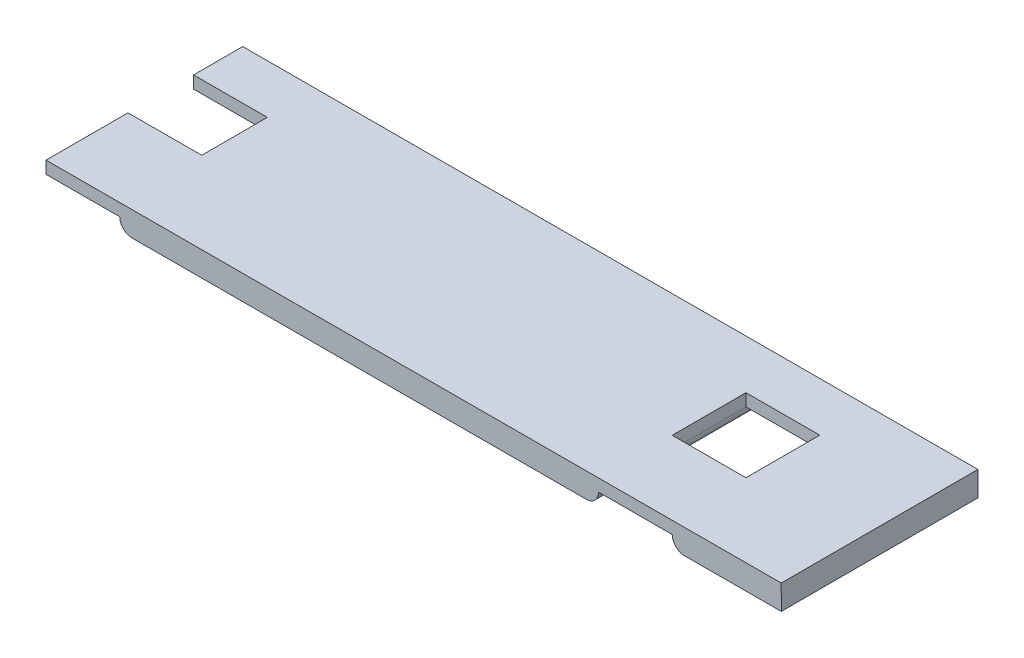
SolidWorks part; units mm, degrees
material "ABS"
ref_plane "X-Y Datum" through (0, 0, 0) normal (0, 0, 1) x (1, 0, 0)
ref_plane "X-Z Datum" through (0, 0, 0) normal (0, 1, 0) x (1, 0, 0)
ref_plane "Y-Z Datum" through (0, 0, 0) normal (1, 0, 0) x (0, 0, -1)
sketch "Sketch7" plane through (0, 0, -1997.112) normal (0, 0, 1) x (1, 0, 0)
  line L0 (-4.5317, 346.4377) -> (19.0716, 346.4821) construction
  line L1 (19.0603, 352.4821) -> (-7.543, 352.432) construction
  line L2 (-7.543, 352.432) -> (-7.5374, 349.432) construction
  line L3 (-4.5317, 346.4377) -> (19.0716, 346.4821)
  line L4 (-25.5373, 349.3981) -> (-25.543, 352.3981)
  line L5 (-25.543, 352.3981) -> (-142.3377, 352.178)
  line L6 (-142.3377, 352.178) -> (-142.332, 349.178)
  line L7 (-139.3264, 346.1836) -> (-28.5317, 346.3924)
  line L8 (-25.5373, 349.3981) -> (-25.543, 352.3981)
  line L9 (-25.543, 352.3981) -> (-142.3377, 352.178)
  line L10 (-142.3377, 352.178) -> (-142.332, 349.178)
  line L11 (-139.3264, 346.1836) -> (-28.5317, 346.3924)
  line L12 (19.0603, 352.4821) -> (-7.543, 352.432)
  line L13 (-7.543, 352.432) -> (-7.5374, 349.432)
  line L14 (19.0603, 352.4821) -> (19.0716, 346.4821)
  arc A0 (-7.5374, 349.432) -> (-4.5317, 346.4377) centre (-4.5374, 349.4376) ccw construction
  arc A1 (-7.5374, 349.432) -> (-4.5317, 346.4377) centre (-4.5374, 349.4376) ccw
  arc A2 (-28.5317, 346.3924) -> (-25.5373, 349.3981) centre (-28.5373, 349.3924) ccw
  arc A3 (-142.332, 349.178) -> (-139.3264, 346.1836) centre (-139.332, 349.1836) ccw
  arc A4 (-28.5317, 346.3924) -> (-25.5373, 349.3981) centre (-28.5373, 349.3924) ccw
  arc A5 (-142.332, 349.178) -> (-139.3264, 346.1836) centre (-139.332, 349.1836) ccw
  dimension "D1" = 0
extrude "Boss-Extrude2" add sketch "Sketch7" along normal blind 48
sketch "Sketch8" plane through (-141.6735, -0.267, 0) normal (-1, -0.0019, 0) x (0, 0, 1)
  line L0 (-1949.112, 352.4456) -> (-1949.112, 349.4456) construction
  line L1 (-1949.112, 352.4456) -> (-1969.112, 352.4456)
  line L2 (-1949.112, 352.4456) -> (-1949.112, 349.4456)
  line L3 (-1949.112, 349.4456) -> (-1969.112, 349.4456)
  line L4 (-1969.112, 352.4456) -> (-1969.112, 349.4456)
  line L5 (-1949.112, 352.4456) -> (-1997.112, 352.4456) construction
  line L6 (-1997.112, 349.4456) -> (-1985.112, 349.4456)
  line L7 (-1997.112, 349.4456) -> (-1997.112, 352.4456)
  line L8 (-1997.112, 352.4456) -> (-1985.112, 352.4456)
  line L9 (-1985.112, 349.4456) -> (-1985.112, 352.4456)
  dimension "D1" = 12
  dimension "D2" = 20
extrude "Boss-Extrude3" add sketch "Sketch8" along normal up to surface (18 mm away)
sketch "Sketch9" plane through (-24.8788, -0.0469, 0) normal (1, 0.0019, 0) x (0, 0, -1)
  line L0 (1949.112, 349.4456) -> (1997.112, 349.4456) construction
  line L1 (1949.112, 352.4456) -> (1967.112, 352.4456)
  line L2 (1949.112, 352.4456) -> (1949.112, 349.4456)
  line L3 (1949.112, 349.4456) -> (1967.112, 349.4456)
  line L4 (1967.112, 352.4456) -> (1967.112, 349.4456)
  line L6 (1997.112, 352.4456) -> (1985.112, 352.4456)
  line L7 (1997.112, 352.4456) -> (1997.112, 349.4456)
  line L8 (1997.112, 349.4456) -> (1985.112, 349.4456)
  line L9 (1985.112, 352.4456) -> (1985.112, 349.4456)
  dimension "D1" = 18
  dimension "D2" = 12
extrude "Boss-Extrude4" add sketch "Sketch9" along normal up to surface (18 mm away) up to face at (-7.5402, 350.932, -1973.112)
